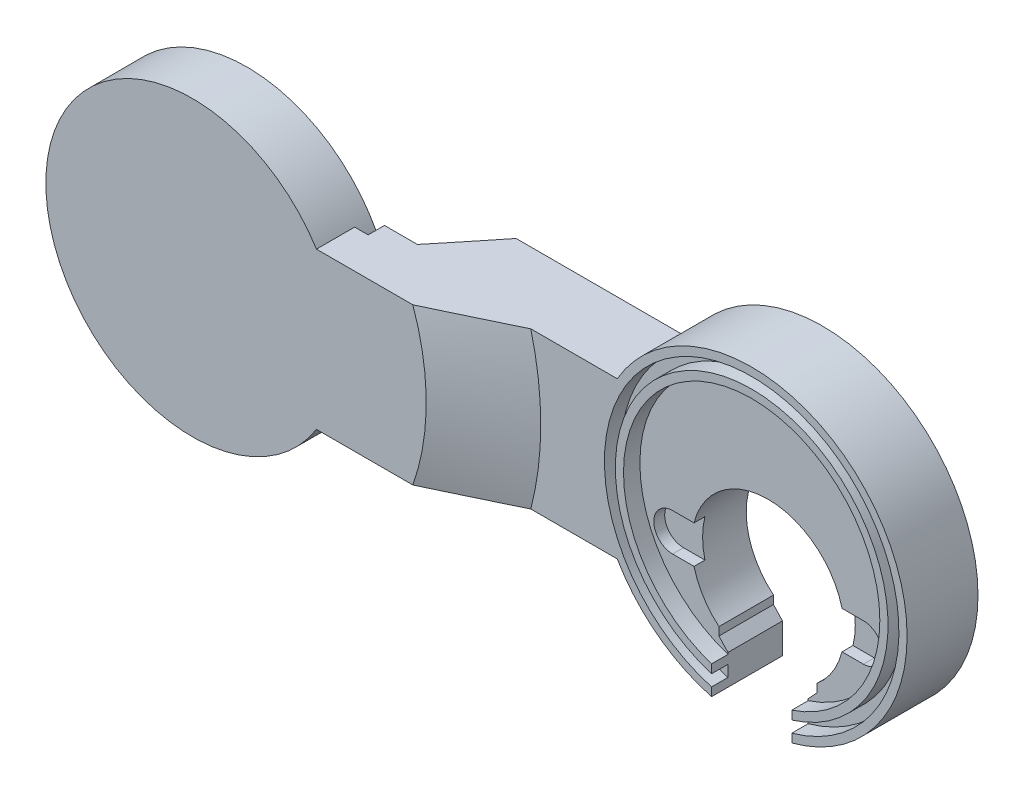
SolidWorks part; units mm, degrees
material "Custom Plastic"
ref_plane "Front Plane" through (0, 0, 0) normal (0, 0, 1) x (1, 0, 0)
ref_plane "Top Plane" through (0, 0, 0) normal (0, 1, 0) x (1, 0, 0)
ref_plane "Right Plane" through (0, 0, 0) normal (1, 0, 0) x (0, 0, -1)
sketch "Sketch1" plane through (0, 0, 0) normal (0, 0, 1) x (1, 0, 0)
  circle A0 centre (0, 0) radius 26.875
  dimension "D1" = 53.75
extrude "Boss-Extrude1" add sketch "Sketch1" along normal blind 2
sketch "Sketch2" plane through (0, 0, 2) normal (0, 0, 1) x (1, 0, 0)
  circle A0 centre (0, 0) radius 26.875
  circle A1 centre (0, 0) radius 25.125
  dimension "D1" = 50.25
  dimension "D2" = 53.75
extrude "Boss-Extrude2" add sketch "Sketch2" along normal blind 8
ref_plane "Plane1" through (0, 0, 20) normal (0, 0, 1) x (1, 0, 0)
sketch "Sketch3" plane through (0, 0, 20) normal (0, 0, 1) x (1, 0, 0)
  line L0 (70.9021, 14.31) -> (22.7484, 14.31)
  line L5 (70.9021, -14.31) -> (22.7484, -14.31)
  arc A2 (70.9021, -14.31) -> (70.9021, 14.31) centre (95.5491, 0) ccw
  circle A3 centre (0, 0) radius 26.875 construction
  arc A4 (22.7484, 14.31) -> (22.7484, -14.31) centre (0, 0) cw
  dimension "D2" = 57
extrude "Boss-Extrude3" add sketch "Sketch3" against normal blind 13 contours A2 L0 A4 L5
chamfer "Chamfer1" distance 20 distance2 15 1 edges at (26.875, 0, 20) first distance on face at (24.8117, 0, 15)
sketch "Sketch4" plane through (0, 0, 7) normal (0, 0, -1) x (-1, 0, 0)
  circle A0 centre (-95.5491, 0) radius 23.5
  circle A1 centre (-95.5491, 0) radius 27
  circle A2 centre (-95.5491, 0) radius 25
  dimension "D1" = 47
  dimension "D2" = 54
  dimension "D3" = 50
extrude "Cut-Extrude1" cut sketch "Sketch4" against normal blind 3 contours A0 | A1 A2 region at (95.5491, 0, 7) region at (121.7855, 0, 7)
sketch "Sketch5" plane through (0, 0, 10) normal (0, 0, -1) x (-1, 0, 0)
  line L0 (-95.5491, 0) -> (-95.5491, -8) construction
  line L5 (-104.5491, -18.7238) -> (-104.5491, -20.2238)
  line L6 (-104.5491, -20.2238) -> (-102.8991, -22)
  line L7 (-102.8991, -22) -> (-102.8991, -27.5359)
  line L9 (-88.1991, -27.5359) -> (-88.1991, -22)
  line L10 (-88.1991, -22) -> (-86.5491, -20.2238)
  line L11 (-86.5491, -20.2238) -> (-86.5491, -18.7238)
  arc A0 (-86.5491, -18.7238) -> (-81.9809, -11.45) centre (-95.5491, -8) ccw
  arc A2 (-81.9809, -4.55) -> (-109.1174, -4.55) centre (-95.5491, -8) ccw
  arc A4 (-109.1174, -11.45) -> (-104.5491, -18.7238) centre (-95.5491, -8) ccw
  arc A5 (-70.9021, 14.31) -> (-70.9021, -14.31) centre (-95.5491, 0) ccw construction
  arc A6 (-102.8991, -27.5359) -> (-88.1991, -27.5359) centre (-95.5491, 0) ccw
  arc A7 (-109.1174, -4.55) -> (-109.1174, -11.45) centre (-95.5491, -8) ccw
  arc A8 (-81.9809, -4.55) -> (-81.9809, -11.45) centre (-95.5491, -8) cw
  dimension "D1" = 8
extrude "Cut-Extrude2" cut sketch "Sketch5" against normal through all both and the other way through all
chamfer "Chamfer2" distance 30 distance2 15 1 edges at (26.875, 0, 7) first distance on face at (75.45, -3.9806, 7)
sketch "Sketch8" plane through (0, 0, 10) normal (0, 0, 1) x (1, 0, 0)
  circle A0 centre (0, 0) radius 25.125
  circle A1 centre (0, 0) radius 26.875
  circle A2 centre (0, 0) radius 29
  line M4 (22.7484, -14.31) -> (31.2548, -14.31)
  line M6 (31.2548, 14.31) -> (22.7484, 14.31)
  dimension "D1" = 53.75
  dimension "D2" = 50.25
  dimension "D3" = 58
extrude "Cut-Extrude4" cut sketch "Sketch8" against normal blind 3 contours A2 A1 M4 M6 region at (26.1042, 7.5277, 10)
sketch "Sketch9" plane through (0, 0, 10) normal (0, 0, -1) x (-1, 0, 0)
  line L0 (-95.5491, 0) -> (-95.5491, -8)
  line L1 (-81.9809, -11.45) -> (-78.0491, -11.45)
  line L2 (-78.0491, -4.55) -> (-81.9809, -4.55)
  line L3 (-109.1174, -4.55) -> (-113.0491, -4.55)
  line L4 (-113.0491, -11.45) -> (-109.1174, -11.45)
  line L5 (-104.5491, -18.7238) -> (-104.5491, -20.2238)
  line L6 (-104.5491, -20.2238) -> (-102.8991, -22)
  line L7 (-102.8991, -22) -> (-102.8991, -25)
  line L8 (-102.8991, -25) -> (-88.1991, -25)
  line L9 (-88.1991, -25) -> (-88.1991, -22)
  line L10 (-88.1991, -22) -> (-86.5491, -20.2238)
  line L11 (-86.5491, -20.2238) -> (-86.5491, -18.7238)
  arc A0 (-86.5491, -18.7238) -> (-81.9809, -11.45) centre (-95.5491, -8) ccw
  arc A1 (-78.0491, -11.45) -> (-78.0491, -4.55) centre (-78.0491, -8) ccw
  arc A2 (-81.9809, -4.55) -> (-109.1174, -4.55) centre (-95.5491, -8) ccw
  arc A3 (-113.0491, -4.55) -> (-113.0491, -11.45) centre (-113.0491, -8) ccw
  arc A4 (-109.1174, -11.45) -> (-104.5491, -18.7238) centre (-95.5491, -8) ccw
  arc M23 (-104.5491, -18.7238) -> (-86.5491, -18.7238) centre (-95.5491, -8) cw
extrude "Cut-Extrude5" cut sketch "Sketch9" against normal blind 2 contours L1 A1 L2 M23 | L3 A3 L4 M23 region at (78.4705, -8, 10) region at (112.6278, -8, 10)
sketch "Sketch10" plane through (0, 0, 2) normal (0, 0, 1) x (1, 0, 0)
  line L0 (-2.5981, -1.5) -> (2.5981, -1.5)
  line L1 (-2.5981, 1.5) -> (2.5981, 1.5)
  line L2 (0, 1.5) -> (0, -1.5) construction
  circle A0 centre (0, 0) radius 5
  arc A1 (-2.5981, 1.5) -> (-2.5981, -1.5) centre (0, 0) ccw
  arc A2 (2.5981, -1.5) -> (2.5981, 1.5) centre (0, 0) ccw
  dimension "D1" = 10
  dimension "D2" = 6
  dimension "D3" = 3
extrude "Boss-Extrude4" add sketch "Sketch10" along normal blind 6
mirror "Mirror2" about plane through (0, 0, 20) normal (0, 0, -1) of bodies 110
delete or keep bodies "Body-Delete/Keep 1" type delete bodies bodies 110
